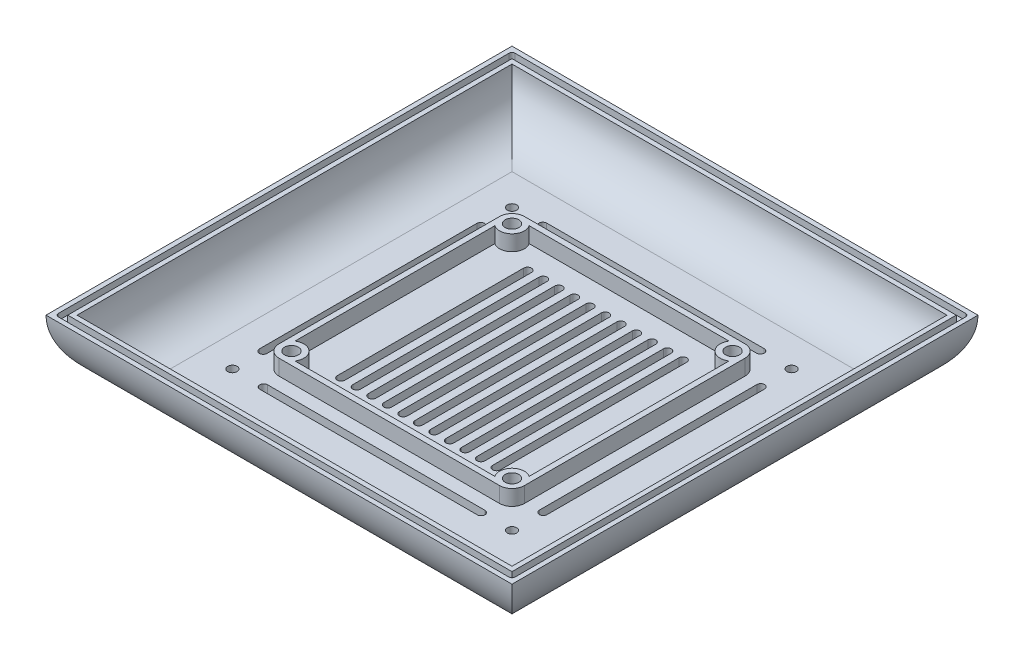
SolidWorks part; units mm, degrees
ref_plane "Front Plane" through (0, 0, 0) normal (0, 0, 1) x (1, 0, 0)
ref_plane "Top Plane" through (0, 0, 0) normal (0, 1, 0) x (1, 0, 0)
ref_plane "Right Plane" through (0, 0, 0) normal (1, 0, 0) x (0, 0, -1)
sketch "Sketch1" plane through (0, 0, 0) normal (0, 1, 0) x (1, 0, 0)
  line L5 (0, 0) -> (150, 0)
  line L6 (0, 0) -> (0, 150)
  line L7 (0, 150) -> (150, 150)
  line L8 (150, 0) -> (150, 150)
extrude "Boss-Extrude1" add sketch "Sketch1" along normal blind 20
fillet "Fillet8" radius 20 4 edges at (0, 0, -75) (75, 0, 0) (150, 0, -75) (75, 0, -150) type face fillet first side face at (75, 0, -75) second side face at (75, 10, 0) second side face at (150, 10, -75) second side face at (75, 10, -150) second side face at (0, 10, -75)
sketch "Sketch3" plane through (0, 0, 0) normal (0, -1, 0) x (1, 0, 0)
  line L0 (75, -20) -> (75, -130) construction
  line L1 (130, -20) -> (20, -20) construction
  line L2 (20, -130) -> (130, -130) construction
  line L3 (20, -75) -> (130, -75) construction
  line L4 (20, -20) -> (20, -130) construction
  line L5 (130, -130) -> (130, -20) construction
  line L6 (20, -20) -> (30, -20) construction
  line L7 (30, -20) -> (30, -130) construction
  line L8 (120, -130) -> (120, -20) construction
  circle A0 centre (30, -30) radius 6
  circle A1 centre (30, -30) radius 4 construction
  circle A2 centre (30, -120) radius 4 construction
  circle A3 centre (30, -120) radius 6
  circle A4 centre (120, -120) radius 6
  circle A5 centre (120, -120) radius 4 construction
  circle A6 centre (120, -30) radius 4 construction
  circle A7 centre (120, -30) radius 6
  dimension "D3" = 10
  dimension "D1" = 10
  dimension "D2" = 10
  dimension "D4" = 10
extrude "Boss-Extrude2" add sketch "Sketch3" along normal blind 7
shell "Shell1" thickness 5 removed face at (75, 20, -75)
sketch "Sketch6" plane through (0, 5, 0) normal (0, 1, 0) x (1, 0, 0)
  line L0 (120, 30) -> (120, 120) construction
  line L1 (120, 120) -> (30, 120) construction
  line L2 (30, 120) -> (30, 30) construction
  line L3 (30, 30) -> (120, 30) construction
  line L4 (39.9341, 120) -> (109.9341, 120) construction
  line L7 (75, 45) -> (75, 105) construction
  line L16 (73.75, 45) -> (73.75, 105)
  line L17 (76.25, 45) -> (76.25, 105)
  line L20 (80, 45) -> (80, 105) construction
  line L23 (78.75, 45) -> (78.75, 105)
  line L26 (81.25, 45) -> (81.25, 105)
  line L29 (85, 45) -> (85, 105) construction
  line L32 (83.75, 45) -> (83.75, 105)
  line L35 (86.25, 45) -> (86.25, 105)
  line L38 (30, 39.9341) -> (30, 109.9341) construction
  line L39 (31.25, 39.9341) -> (31.25, 109.9341)
  line L40 (28.75, 39.9341) -> (28.75, 109.9341)
  line L41 (90, 45) -> (90, 105) construction
  line L44 (88.75, 45) -> (88.75, 105)
  line L47 (91.25, 45) -> (91.25, 105)
  line L50 (95, 45) -> (95, 105) construction
  line L53 (93.75, 45) -> (93.75, 105)
  line L56 (96.25, 45) -> (96.25, 105)
  line L59 (100, 45) -> (100, 105) construction
  line L62 (30, 30) -> (30, 120) construction
  line L63 (20, 75) -> (130, 75) construction
  line L64 (20, 20) -> (20, 130) construction
  line L65 (130, 130) -> (130, 20) construction
  line L66 (98.75, 45) -> (98.75, 105)
  line L69 (101.25, 45) -> (101.25, 105)
  line L70 (70, 45) -> (70, 105) construction
  line L71 (68.75, 45) -> (68.75, 105)
  line L72 (71.25, 45) -> (71.25, 105)
  line L73 (65, 45) -> (65, 105) construction
  line L74 (63.75, 45) -> (63.75, 105)
  line L75 (66.25, 45) -> (66.25, 105)
  line L76 (60, 45) -> (60, 105) construction
  line L77 (58.75, 45) -> (58.75, 105)
  line L78 (61.25, 45) -> (61.25, 105)
  line L79 (55, 45) -> (55, 105) construction
  line L80 (53.75, 45) -> (53.75, 105)
  line L81 (56.25, 45) -> (56.25, 105)
  line L82 (50, 45) -> (50, 105) construction
  line L83 (48.75, 45) -> (48.75, 105)
  line L84 (51.25, 45) -> (51.25, 105)
  line L85 (39.9341, 118.75) -> (109.9341, 118.75)
  line L86 (39.9341, 121.25) -> (109.9341, 121.25)
  line L87 (120, 110.0659) -> (120, 40.0659) construction
  line L88 (118.75, 110.0659) -> (118.75, 40.0659)
  line L89 (121.25, 110.0659) -> (121.25, 40.0659)
  line L90 (110.0659, 30) -> (40.0659, 30) construction
  line L91 (110.0659, 31.25) -> (40.0659, 31.25)
  line L92 (110.0659, 28.75) -> (40.0659, 28.75)
  arc A22 (31.25, 39.9341) -> (28.75, 39.9341) centre (30, 39.9341) cw
  arc A23 (28.75, 109.9341) -> (31.25, 109.9341) centre (30, 109.9341) cw
  circle A38 centre (39.5, 110.5) radius 4 construction
  circle A39 centre (39.5, 39.5) radius 4 construction
  circle A40 centre (110.5, 110.5) radius 4 construction
  circle A41 centre (110.5, 39.5) radius 4 construction
  arc A44 (73.75, 45) -> (76.25, 45) centre (75, 45) ccw
  arc A45 (76.25, 105) -> (73.75, 105) centre (75, 105) ccw
  arc A46 (78.75, 45) -> (81.25, 45) centre (80, 45) ccw
  arc A47 (81.25, 105) -> (78.75, 105) centre (80, 105) ccw
  arc A48 (83.75, 45) -> (86.25, 45) centre (85, 45) ccw
  arc A49 (86.25, 105) -> (83.75, 105) centre (85, 105) ccw
  arc A50 (88.75, 45) -> (91.25, 45) centre (90, 45) ccw
  arc A51 (91.25, 105) -> (88.75, 105) centre (90, 105) ccw
  arc A52 (93.75, 45) -> (96.25, 45) centre (95, 45) ccw
  arc A53 (96.25, 105) -> (93.75, 105) centre (95, 105) ccw
  arc A54 (98.75, 45) -> (101.25, 45) centre (100, 45) ccw
  arc A55 (101.25, 105) -> (98.75, 105) centre (100, 105) ccw
  arc A56 (68.75, 45) -> (71.25, 45) centre (70, 45) ccw
  arc A57 (71.25, 105) -> (68.75, 105) centre (70, 105) ccw
  arc A58 (63.75, 45) -> (66.25, 45) centre (65, 45) ccw
  arc A59 (66.25, 105) -> (63.75, 105) centre (65, 105) ccw
  arc A60 (58.75, 45) -> (61.25, 45) centre (60, 45) ccw
  arc A61 (61.25, 105) -> (58.75, 105) centre (60, 105) ccw
  arc A62 (53.75, 45) -> (56.25, 45) centre (55, 45) ccw
  arc A63 (56.25, 105) -> (53.75, 105) centre (55, 105) ccw
  arc A64 (48.75, 45) -> (51.25, 45) centre (50, 45) ccw
  arc A65 (51.25, 105) -> (48.75, 105) centre (50, 105) ccw
  arc A66 (39.9341, 118.75) -> (39.9341, 121.25) centre (39.9341, 120) cw
  arc A67 (109.9341, 121.25) -> (109.9341, 118.75) centre (109.9341, 120) cw
  arc A68 (118.75, 110.0659) -> (121.25, 110.0659) centre (120, 110.0659) cw
  arc A69 (121.25, 40.0659) -> (118.75, 40.0659) centre (120, 40.0659) cw
  arc A70 (110.0659, 31.25) -> (110.0659, 28.75) centre (110.0659, 30) cw
  arc A71 (40.0659, 28.75) -> (40.0659, 31.25) centre (40.0659, 30) cw
  point P13 (74.9341, 120)
  point P17 (75, 75)
  point P23 (75, 75)
  point P25 (80, 75)
  point P32 (85, 75)
  point P39 (90, 75)
  point P46 (95, 75)
  point P53 (100, 75)
  point P60 (70, 75)
  point P67 (65, 75)
  point P74 (60, 75)
  point P81 (55, 75)
  point P89 (30, 74.9341)
  point P95 (50, 75)
  point P105 (120, 75.0659)
  point P112 (75.0659, 30)
  point P117 (75, 75)
  dimension "D1" = 4
  dimension "D5" = 35.5
extrude "Cut-Extrude2" cut sketch "Sketch6" against normal blind 7
sketch "Sketch7" plane through (0, 5, 0) normal (0, 1, 0) x (1, 0, 0)
  line L0 (20, 75) -> (130, 75) construction
  line L1 (20, 20) -> (20, 130) construction
  line L2 (130, 130) -> (130, 20) construction
  line L3 (75, 130) -> (75, 20) construction
  line L4 (20, 130) -> (130, 130) construction
  line L5 (130, 20) -> (20, 20) construction
  line L7 (106.5, 110.5) -> (114.5, 110.5) construction
  line L9 (106.5, 39.5) -> (114.5, 39.5) construction
  line L10 (114.5, 110.5) -> (114.5, 39.5)
  line L11 (39.5, 35.5) -> (110.5, 35.5)
  line L12 (39.5, 35.5) -> (39.5, 43.5) construction
  line L14 (110.5, 35.5) -> (110.5, 43.5) construction
  line L15 (35.5, 39.5) -> (43.5, 39.5) construction
  line L16 (35.5, 39.5) -> (35.5, 110.5)
  line L17 (35.5, 110.5) -> (43.5, 110.5) construction
  line L19 (39.5, 114.5) -> (110.5, 114.5)
  line L20 (39.5, 114.5) -> (39.5, 106.5) construction
  line L22 (110.5, 114.5) -> (110.5, 106.5) construction
  line L23 (42.8407, 37.3) -> (107.1593, 37.3)
  line L24 (37.3, 107.1593) -> (37.3, 42.8407)
  line L25 (107.1593, 112.7) -> (42.8407, 112.7)
  line L26 (112.7, 42.8407) -> (112.7, 107.1593)
  circle A0 centre (110.5, 110.5) radius 2.2
  circle A1 centre (39.5, 110.5) radius 2.2
  circle A2 centre (39.5, 39.5) radius 2.2
  circle A3 centre (110.5, 39.5) radius 2.2
  arc A5 (114.5, 110.5) -> (110.5, 114.5) centre (110.5, 110.5) ccw
  arc A6 (35.5, 110.5) -> (39.5, 114.5) centre (39.5, 110.5) cw
  arc A7 (114.5, 39.5) -> (110.5, 35.5) centre (110.5, 39.5) cw
  arc A8 (35.5, 39.5) -> (39.5, 35.5) centre (39.5, 39.5) ccw
  circle A9 centre (110.5, 39.5) radius 4 construction
  circle A10 centre (39.5, 39.5) radius 4 construction
  arc A12 (112.7, 107.1593) -> (107.1593, 112.7) centre (110.5, 110.5) cw
  arc A13 (37.3, 42.8407) -> (42.8407, 37.3) centre (39.5, 39.5) cw
  arc A14 (42.8407, 112.7) -> (37.3, 107.1593) centre (39.5, 110.5) cw
  arc A15 (112.7, 42.8407) -> (107.1593, 37.3) centre (110.5, 39.5) ccw
  point P49 (75, 75)
  dimension "D1" = 35.5
  dimension "D4" = 4
  dimension "D2" = 35.5
extrude "Boss-Extrude3" add sketch "Sketch7" along normal blind 5
sketch "Sketch8" plane through (0, 5, 0) normal (0, 1, 0) x (1, 0, 0)
  circle A0 centre (110.5, 110.5) radius 2.2
  circle A1 centre (110.5, 39.5) radius 2.2
  circle A2 centre (39.5, 110.5) radius 2.2
  circle A3 centre (39.5, 39.5) radius 2.2
extrude "Cut-Extrude3" cut sketch "Sketch8" against normal through all
sketch "Sketch11" plane through (0, -7, 0) normal (0, -1, 0) x (1, 0, 0)
  line L0 (75, -20) -> (75, -130) construction
  line L1 (130, -20) -> (20, -20) construction
  line L2 (20, -130) -> (130, -130) construction
  line L3 (130, -75) -> (20, -75) construction
  line L4 (130, -130) -> (130, -20) construction
  line L5 (20, -20) -> (20, -130) construction
  circle A0 centre (30, -30) radius 4
  circle A1 centre (120, -30) radius 4
  circle A2 centre (120, -120) radius 4
  circle A3 centre (30, -120) radius 4
extrude "Cut-Extrude4" cut sketch "Sketch11" against normal up to next
sketch "Sketch12" plane through (0, 5, 0) normal (0, 1, 0) x (1, 0, 0)
  line L0 (75, 130) -> (75, 20) construction
  line L1 (20, 130) -> (130, 130) construction
  line L2 (130, 20) -> (20, 20) construction
  line L3 (20, 75) -> (130, 75) construction
  line L4 (20, 20) -> (20, 130) construction
  line L5 (130, 130) -> (130, 20) construction
  circle A0 centre (30, 120) radius 4
  circle A1 centre (30, 120) radius 1.5
  circle A2 centre (120, 120) radius 1.5
  circle A3 centre (120, 120) radius 4
  circle A4 centre (120, 30) radius 4
  circle A5 centre (120, 30) radius 1.5
  circle A6 centre (30, 30) radius 1.5
  circle A7 centre (30, 30) radius 4
extrude "Boss-Extrude4" add sketch "Sketch12" against normal blind 5
sketch "Sketch13" plane through (0, 20, 0) normal (0, 1, 0) x (1, 0, 0)
  line L0 (147.5, 147.5) -> (2.5, 147.5) construction
  line L1 (146.5, 146.5) -> (3.5, 146.5)
  line L2 (2.5, 147.5) -> (2.5, 2.5) construction
  line L3 (3.5, 146.5) -> (3.5, 3.5)
  line L4 (1.5, 147.5) -> (1.5, 2.5)
  line L5 (147.5, 148.5) -> (2.5, 148.5)
  line L6 (147.5, 2.5) -> (147.5, 147.5) construction
  line L7 (146.5, 3.5) -> (146.5, 146.5)
  line L8 (148.5, 2.5) -> (148.5, 147.5)
  line L9 (2.5, 2.5) -> (147.5, 2.5) construction
  line L10 (3.5, 3.5) -> (146.5, 3.5)
  line L11 (2.5, 1.5) -> (147.5, 1.5)
  arc A0 (2.5, 148.5) -> (1.5, 147.5) centre (2.5, 147.5) ccw
  arc A1 (1.5, 2.5) -> (2.5, 1.5) centre (2.5, 2.5) ccw
  arc A2 (148.5, 147.5) -> (147.5, 148.5) centre (147.5, 147.5) ccw
  arc A4 (147.5, 1.5) -> (148.5, 2.5) centre (147.5, 2.5) ccw
  point P4 (75, 2.5)
  point P10 (2.5, 75)
  point P16 (75, 147.5)
  point P23 (147.5, 75)
  point P30 (75, 2.5)
  point P35 (75, 75)
extrude "Cut-Extrude5" cut sketch "Sketch13" against normal blind 2
